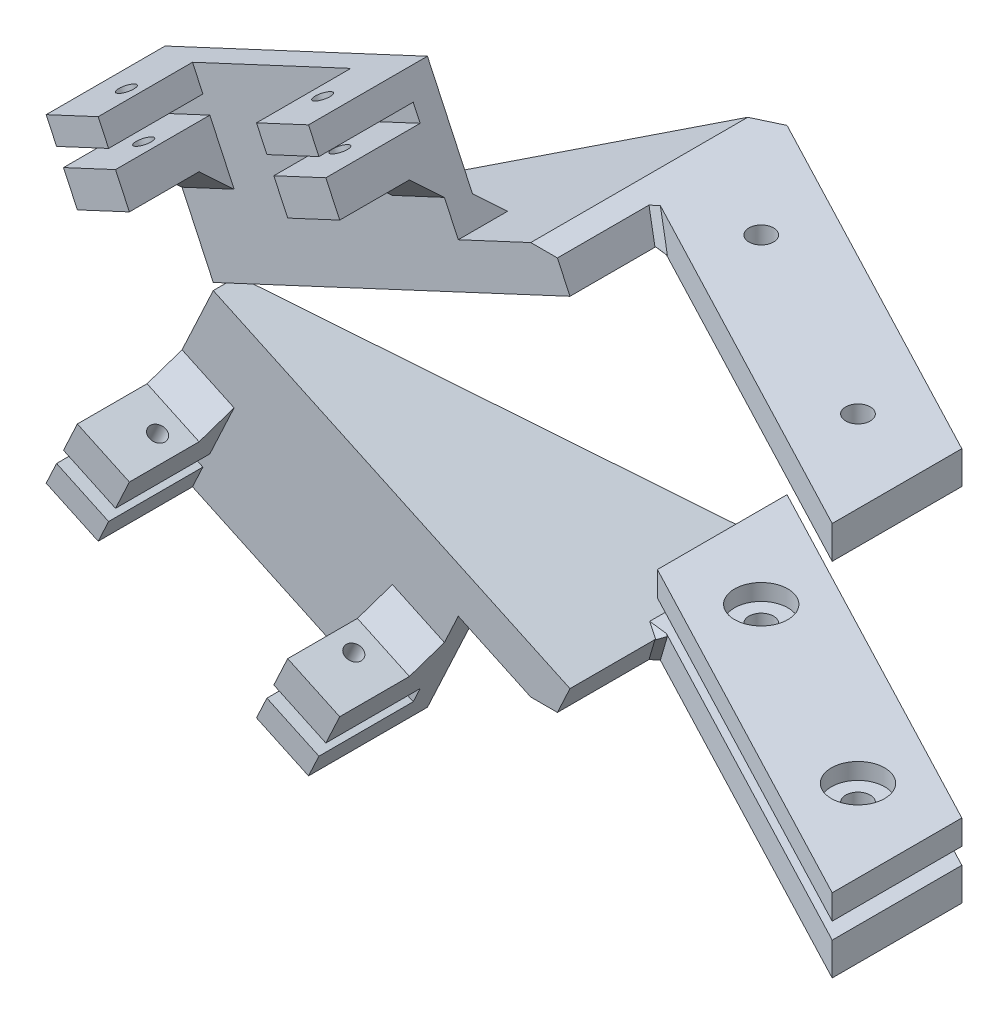
SolidWorks part; units mm, degrees
ref_plane "Front Plane" through (0, 0, 0) normal (0, 0, 1) x (1, 0, 0)
ref_plane "Top Plane" through (0, 0, 0) normal (0, 1, 0) x (1, 0, 0)
ref_plane "Right Plane" through (0, 0, 0) normal (1, 0, 0) x (0, 0, -1)
sketch "Sketch1" plane through (0, 0, 0) normal (0, 1, 0) x (1, 0, 0)
  line L0 (0, 6) -> (0, -19) construction
  line L1 (0, -19) -> (24.7992, -19) construction
  circle A0 centre (0, 0) radius 6
  circle A1 centre (24.7992, -13) radius 6
  dimension "D1" = 28
  dimension "D2" = 12
  dimension "D3" = 12
  dimension "D4" = 25
sketch "Sketch3" plane through (0, 0, 0) normal (0, 1, 0) x (1, 0, 0)
  line L0 (-10, 13.1456) -> (-10, -2.6614)
  line L1 (-10, -2.6614) -> (34.7992, -26.1456)
  line L2 (34.7992, -26.1456) -> (34.7992, -10.3386)
  line L3 (34.7992, -10.3386) -> (-10, 13.1456)
  line L5 (0, 0) -> (24.7992, -13) construction
  line L6 (0, 6) -> (0, -19) construction
  dimension "D1" = 7
  dimension "D2" = 7
  dimension "D3" = 10
  dimension "D4" = 10
extrude "Boss-Extrude1" add sketch "Sketch3" along normal blind 3
extrude "Boss-Extrude3" add sketch "Sketch1" against normal blind 2
sketch "Sketch4" plane through (0, 3, 0) normal (0, 1, 0) x (1, 0, 0)
  circle A0 centre (0, 0) radius 1.5
  circle A1 centre (24.7992, -13) radius 1.5
  dimension "D1" = 3
  dimension "D2" = 3
extrude "Cut-Extrude1" cut sketch "Sketch4" against normal through all
sketch "Sketch5" plane through (0, 3, 0) normal (0, 1, 0) x (1, 0, 0)
  circle A0 centre (0, 0) radius 3.25
  circle A1 centre (24.7992, -13) radius 3.25
  dimension "D1" = 6.5
  dimension "D2" = 6.5
extrude "Cut-Extrude2" cut sketch "Sketch5" against normal blind 2
sketch "Sketch6" plane through (0, -2, 0) normal (0, -1, 0) x (1, 0, 0)
  line L0 (-10, 2.6614) -> (-10, -13.1456)
  line L1 (-10, -13.1456) -> (34.7992, 10.3386)
  line L2 (34.7992, 10.3386) -> (34.7992, 26.1456)
  line L3 (34.7992, 26.1456) -> (-10, 2.6614)
  circle A0 centre (0, 0) radius 1.5
  circle A1 centre (24.7992, 13) radius 1.5
  circle A2 centre (24.7992, 13) radius 1.5 construction
  circle A3 centre (0, 0) radius 1.5 construction
extrude "Boss-Extrude4" add sketch "Sketch6" along normal blind 4 separate body
sketch "Sketch12" plane through (0, 0, 0) normal (0, 0, 1) x (1, 0, 0)
  line L0 (-10, -2) -> (-10, -6.5315)
  line L1 (-10, -6.5315) -> (-12.1131, -6.5315)
  line L2 (-12.1131, -6.5315) -> (-10, -2)
  line L3 (-10, -2) -> (-1.422, -6)
  line L4 (34.7992, -6) -> (-10, -6) construction
  line L5 (-10, -6.5315) -> (-11.7357, -5.7222)
  dimension "D1" = 25
  dimension "D2" = 5
ref_plane "Plane1" through (0, -6.5315, 0) normal (0, -1, 0) x (-1, 0, 0)
ref_plane "Plane2" through (-2.5521, -5.473, 0) normal (0.4226, 0.9063, 0) x (0.9063, -0.4226, 0)
sketch "Sketch19" plane through (-2.5521, -5.473, 0) normal (0.4226, 0.9063, 0) x (0.9063, -0.4226, 0)
  line L0 (-6.5274, 13.1456) -> (-6.5274, -14.8544)
  line L2 (-6.5274, -14.8544) -> (-54.5274, -14.8544)
  line L3 (-54.5274, -14.8544) -> (-54.5274, 13.1456)
  line L4 (-54.5274, 13.1456) -> (-6.5274, 13.1456)
  dimension "D1" = 48
  dimension "D2" = 28
extrude "Boss-Extrude9" add sketch "Sketch19" against normal blind 5
sketch "Sketch22" plane through (0, 0, 14.8544) normal (0, 0, 1) x (1, 0, 0)
  line L0 (-51.9707, 17.5713) -> (-60.8457, -1.4612)
  line L1 (-60.8457, -1.4612) -> (-28.853, -16.3796)
  line L2 (-28.853, -16.3796) -> (-19.978, 2.6528)
  line L3 (-51.9707, 17.5713) -> (-8.4679, -2.7144) construction
  line L4 (-19.978, 2.6528) -> (-51.9707, 17.5713)
  dimension "D1" = 21
  dimension "D2" = 35.3
extrude "Boss-Extrude10" add sketch "Sketch22" against normal blind 3
sketch "Sketch23" plane through (0, 0, 14.8544) normal (0, 0, 1) x (1, 0, 0)
  line L0 (-58.7326, 3.0703) -> (-57.0421, 6.6956)
  line L1 (-60.8457, -1.4612) -> (-51.9707, 17.5713) construction
  line L2 (-57.0421, 6.6956) -> (-50.6979, 3.7372)
  line L3 (-50.6979, 3.7372) -> (-52.3884, 0.112)
  line L4 (-52.3884, 0.112) -> (-58.7326, 3.0703)
  line L5 (-60.8457, -1.4612) -> (-59.5778, 1.2577)
  line L6 (-59.5778, 1.2577) -> (-53.2337, -1.7006)
  line L7 (-53.2337, -1.7006) -> (-54.5015, -4.4195)
  line L8 (-60.8457, -1.4612) -> (-28.853, -16.3796) construction
  line L9 (-54.5015, -4.4195) -> (-60.8457, -1.4612)
  line L10 (-44.8493, -8.9204) -> (-35.9744, 10.112) construction
  line L11 (-51.9707, 17.5713) -> (-8.4679, -2.7144) construction
  line L12 (-35.1972, -13.4213) -> (-28.853, -16.3796)
  line L13 (-33.9293, -10.7024) -> (-35.1972, -13.4213)
  line L14 (-27.5851, -13.6607) -> (-33.9293, -10.7024)
  line L15 (-28.853, -16.3796) -> (-27.5851, -13.6607)
  line L16 (-33.0841, -8.8898) -> (-26.7399, -11.8481)
  line L17 (-31.3936, -5.2645) -> (-33.0841, -8.8898)
  line L18 (-25.0494, -8.2229) -> (-31.3936, -5.2645)
  line L19 (-26.7399, -11.8481) -> (-25.0494, -8.2229)
  dimension "D1" = 4
  dimension "D2" = 7
  dimension "D3" = 3
  dimension "D4" = 2
extrude "Boss-Extrude11" add sketch "Sketch23" along normal blind 11.5
sketch "Sketch24" plane through (-11.4271, -24.5055, 0) normal (-0.4226, -0.9063, 0) x (0.9063, -0.4226, 0)
  line L0 (-47.5274, 20.6044) -> (-50.0774, 20.6044) construction
  line L1 (-47.5274, 26.3544) -> (-47.5274, 14.8544) construction
  line L2 (-36.8774, 14.8544) -> (-36.8774, 11.8544) construction
  line L3 (-47.5274, 14.8544) -> (-26.2274, 14.8544) construction
  line L4 (-19.2274, 11.8544) -> (-54.5274, 11.8544) construction
  circle A0 centre (-50.0774, 20.6044) radius 1
  circle A1 centre (-23.6774, 20.6044) radius 1
  dimension "D1" = 2.55
  dimension "D2" = 2
extrude "Cut-Extrude3" cut sketch "Sketch24" against normal through all
sketch "Sketch25" plane through (0, -6, 0) normal (0, -1, 0) x (1, 0, 0)
  line L0 (-1.7598, -8.826) -> (-0.856, -22.3434)
  line L1 (-10, -13.1456) -> (34.7992, 10.3386) construction
  line L2 (-0.856, -22.3434) -> (-19.4164, -22.3434)
  line L3 (-19.4164, -22.3434) -> (-12.5617, 28.5921)
  line L4 (-12.5617, 28.5921) -> (-0.856, 28.5921)
  line L5 (-0.856, 28.5921) -> (-1.7598, -8.826)
extrude "Cut-Extrude4" cut sketch "Sketch25" along normal through all
sketch "Sketch26" plane through (3.25, 0, -6.1998) normal (0.4643, 0, -0.8857) x (-0.8857, 0, -0.4643)
  line L0 (-2.6472, -3.4709) -> (-2.0453, -11.2945)
  line L1 (-2.0453, -11.2945) -> (36.033, -14.5224)
  line L2 (36.033, -14.5224) -> (23.9967, 7.0882)
  line L3 (23.9967, 7.0882) -> (-2.6472, -3.4709)
extrude "Cut-Extrude5" cut sketch "Sketch26" along normal through all
chamfer "Chamfer2" distance 1 angle 45 2 edges at (-9.234, -2.3572, 3.0629) (-9.234, -4.3572, 3.0629)
chamfer "Chamfer3" distance 25 distance2 48 1 edges at (-53.0272, 15.3055, -13.1456)
chamfer "Chamfer4" distance 3 angle 45 1 edges at (-38.0874, 5.5805, 11.8544)
chamfer "Chamfer5" distance 3 angle 45 2 edges at (-53.87, 5.2164, 14.8544) (-28.2215, -6.7437, 14.8544)
ref_plane "Plane3" through (0, 18, 0) normal (0, 1, 0) x (1, 0, 0)
mirror "Mirror1" about plane through (0, 18, 0) normal (0, 1, 0) of bodies 135
